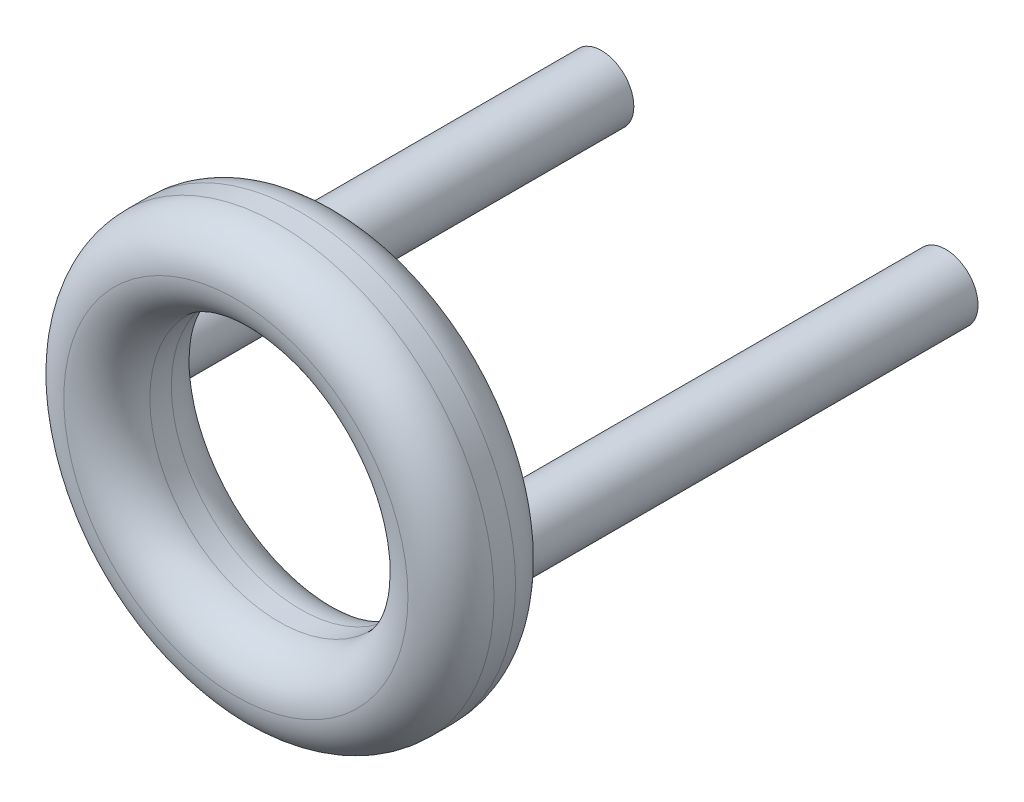
SolidWorks part; units mm, degrees
ref_plane "Plan de face" through (0, 0, 0) normal (0, 0, 1) x (1, 0, 0)
ref_plane "Plan de dessus" through (0, 0, 0) normal (0, 1, 0) x (1, 0, 0)
ref_plane "Plan de droite" through (0, 0, 0) normal (1, 0, 0) x (0, 0, -1)
sketch "Esquisse1" plane through (0, 0, 0) normal (0, 0, 1) x (1, 0, 0)
  circle A0 centre (0, 0) radius 30
  circle A1 centre (0, 0) radius 50
  dimension "D1" = 60
  dimension "D2" = 100
extrude "Boss.-Extru.2" add sketch "Esquisse1" along normal blind 25
sketch "Esquisse4" plane through (0, 0, 0) normal (0, 0, 1) x (1, 0, 0)
  circle A0 centre (-40, 0) radius 7.5
  circle A1 centre (40, 0) radius 7.5
  dimension "D1" = 15
  dimension "D2" = 15
  dimension "D3" = 40
  dimension "D4" = 40
extrude "Boss.-Extru.3" add sketch "Esquisse4" against normal blind 100
fillet "Congé1" radius 10 1 edges at (50, 0, 25)
fillet "Congé2" radius 10 1 edges at (50, 0, 0)
fillet "Congé3" radius 10 1 edges at (30, 0, 25)
fillet "Congé4" radius 10 1 edges at (30, 0, 0)
